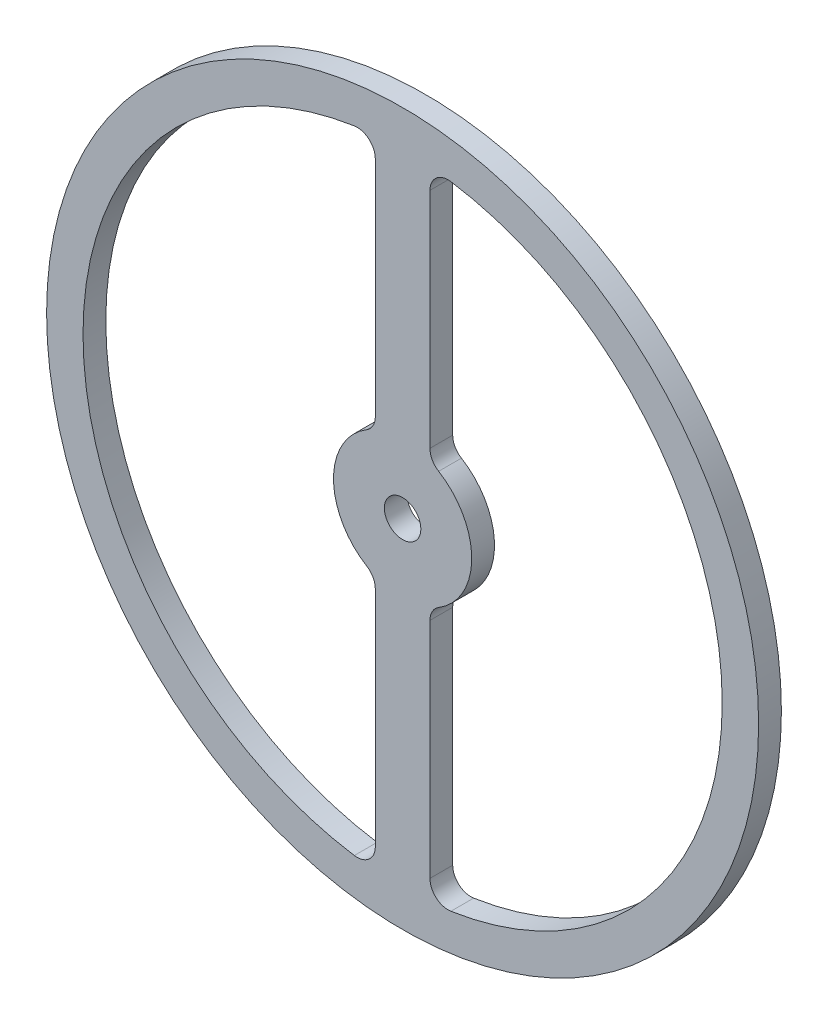
SolidWorks part; units mm, degrees
ref_plane "Front Plane" through (0, 0, 0) normal (0, 0, 1) x (1, 0, 0)
ref_plane "Top Plane" through (0, 0, 0) normal (0, 1, 0) x (1, 0, 0)
ref_plane "Right Plane" through (0, 0, 0) normal (1, 0, 0) x (0, 0, -1)
sketch "Sketch1" plane through (0, 0, 0) normal (0, 0, 1) x (1, 0, 0)
  circle A0 centre (0, 0) radius 49.657
  dimension "D1" = 99.314
extrude "Boss-Extrude1" add sketch "Sketch1" along normal blind 3.175
ref_axis "Axis1" through (0, 0, 32.1057) along (0, 0, -1)
sketch "Sketch3" plane through (0, 0, 3.175) normal (0, 0, 1) x (1, 0, 0)
  line L0 (-3.81, 44.4139) -> (-3.81, 8.8539)
  line L1 (-3.81, -8.8539) -> (-3.81, -44.4139)
  line L2 (0, 0) -> (0, 49.657) construction
  line L3 (0, 0) -> (0, -49.657) construction
  line L8 (3.81, 8.8539) -> (3.81, 44.4139)
  line L9 (3.81, -44.4139) -> (3.81, -8.8539)
  arc A0 (-3.81, 44.4139) -> (-3.81, -44.4139) centre (0, 0) ccw
  arc A1 (-3.81, 8.8539) -> (-3.81, -8.8539) centre (0, 0) ccw
  circle A2 centre (0, 0) radius 49.657 construction
  arc A7 (3.81, -44.4139) -> (3.81, 44.4139) centre (0, 0) ccw
  arc A8 (3.81, -8.8539) -> (3.81, 8.8539) centre (0, 0) ccw
  point P18 (0, 0)
  dimension "D2" = 180
  dimension "D3" = 3.81
  dimension "D5" = 5.08
  dimension "D1" = 35.56
  dimension "D4" = 3.81
  dimension "D6" = 2
extrude "Cut-Extrude1" cut sketch "Sketch3" against normal through all
fillet "Fillet1" radius 2.54 4 edges at (-3.81, -44.4139, 1.5875) (-3.81, 44.4139, 1.5875) (3.81, -44.4139, 1.5875) (3.81, 44.4139, 1.5875)
fillet "Fillet2" radius 2.54 4 edges at (-3.81, -8.8539, 1.5875) (-3.81, 8.8539, 1.5875) (3.81, 8.8539, 1.5875) (3.81, -8.8539, 1.5875)
sketch "Sketch4" plane through (0, 0, 3.175) normal (0, 0, 1) x (1, 0, 0)
  circle A0 centre (0, 0) radius 2.54
  dimension "D1" = 5.08
extrude "Cut-Extrude2" cut sketch "Sketch4" against normal through all
equation "\"D4@Sketch3\"=\"D3@Sketch3\""
